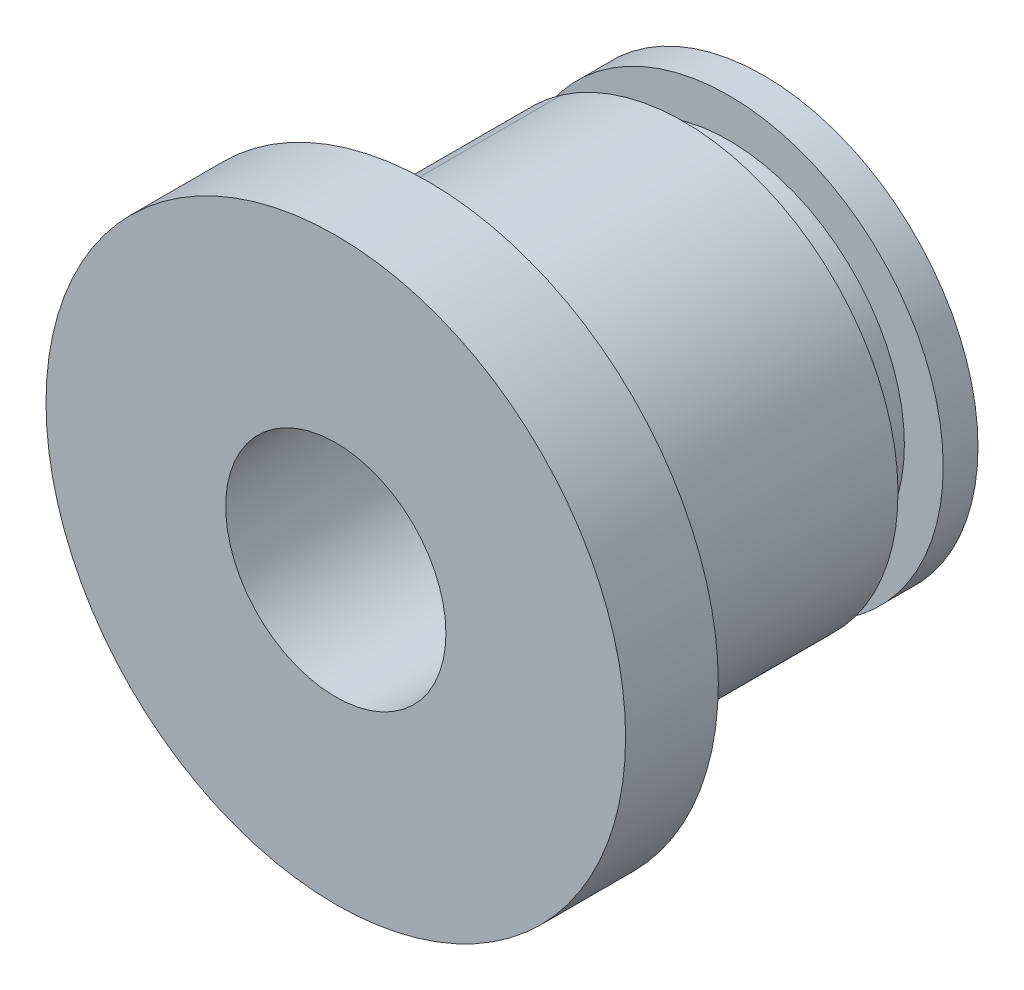
SolidWorks part; units mm, degrees
material "AISI 4130 Steel, annealed at 865C"
ref_plane "Front Plane" through (0, 0, 0) normal (0, 0, 1) x (1, 0, 0)
ref_plane "Top Plane" through (0, 0, 0) normal (0, 1, 0) x (1, 0, 0)
ref_plane "Right Plane" through (0, 0, 0) normal (1, 0, 0) x (0, 0, -1)
sketch "Sketch1" plane through (0, 0, 0) normal (0, 0, 1) x (1, 0, 0)
  circle A0 centre (0, 0) radius 6.35
  dimension "D1" = 12.7
extrude "Boss-Extrude1" add sketch "Sketch1" along normal blind 2.032
sketch "Sketch2" plane through (0, 0, 0) normal (0, 0, -1) x (-1, 0, 0)
  circle A0 centre (0, 0) radius 4.699
  dimension "D1" = 9.398
extrude "Boss-Extrude2" add sketch "Sketch2" along normal blind 7.3406
ref_axis "Axis1" through (0, 0, 6.5491) along (0, 0, -1)
sketch "Sketch4" plane through (0, 0, 0) normal (1, 0, 0) x (0, 0, -1)
  line L0 (0, -4.699) -> (0, 4.699) construction
  line L1 (0, -4.699) -> (0, 4.699)
  line L2 (5.588, 4.699) -> (5.588, -4.699)
  line L3 (7.3406, 4.699) -> (0, 4.699) construction
  line L4 (0, -4.699) -> (7.3406, -4.699) construction
  line L5 (0, 4.699) -> (7.3406, 4.699)
  line L6 (0, -4.699) -> (7.3406, -4.699)
  line L7 (7.3406, -4.699) -> (7.3406, 4.699) construction
  line L8 (6.5786, 4.699) -> (6.5786, -4.699)
  line L9 (5.588, 3.8481) -> (6.5786, 3.8481)
  line L10 (5.588, 0) -> (6.5786, 0)
  dimension "D1" = 5.588
  dimension "D2" = 0.9906
  dimension "D3" = 3.8481
revolve "Cut-Revolve1" cut sketch "Sketch4" angle 360 about axis through (0, 0, 6.5491) along (0, 0, -1) region at (0, 4.2735, -6.0833)
sketch3d "3DSketch1"
  line L0 (2.6418, -3.886, 0) -> (-2.6678, 3.8683, 0)
  circle A2 centre (0, 0, 0) radius 4.699 construction
  point P4 (0, 0, -4.699)
split line "Split Line3"
sketch "Sketch8" plane through (0, 0, 2.032) normal (0, 0, 1) x (1, 0, 0)
  circle A0 centre (0, 0) radius 2.413
extrude "Cut-Extrude2" cut sketch "Sketch8" against normal blind 15.24
